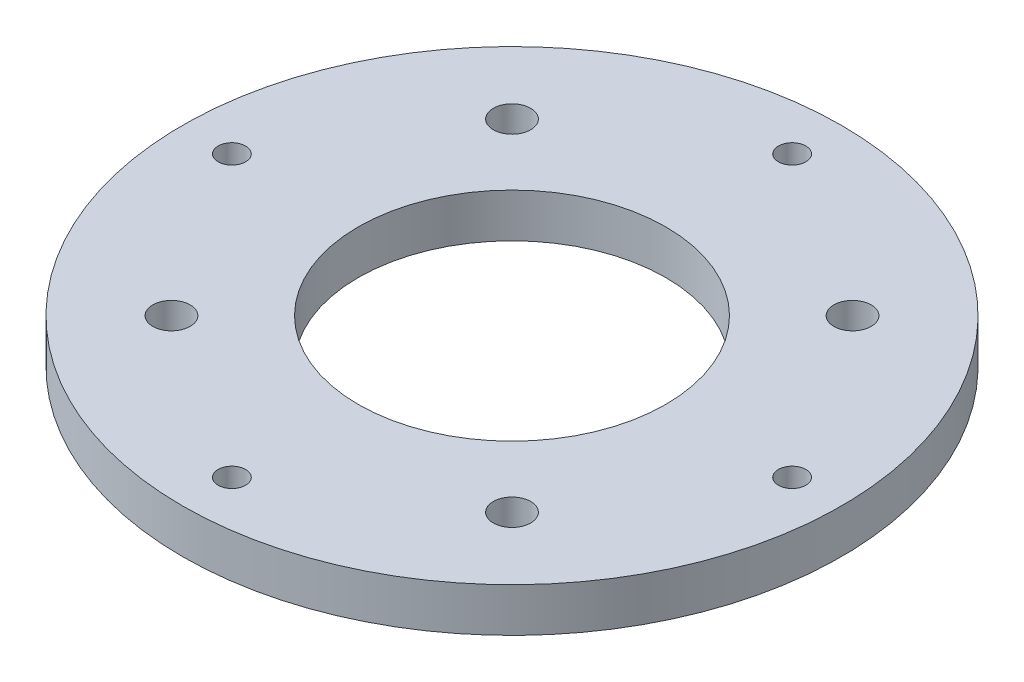
SolidWorks part; units mm, degrees
material "Acrylic (Medium-high impact)"
ref_plane "Front Plane" through (0, 0, 0) normal (0, 0, 1) x (1, 0, 0)
ref_plane "Top Plane" through (0, 0, 0) normal (0, 1, 0) x (1, 0, 0)
ref_plane "Right Plane" through (0, 0, 0) normal (1, 0, 0) x (0, 0, -1)
sketch "Sketch1" plane through (0, 0, 0) normal (0, 1, 0) x (1, 0, 0)
  circle A0 centre (0, 0) radius 30
  dimension "D1" = 60
base flange "Base-Flange1" sketch "Sketch1" thickness 4 reverse thickness direction no parameters "D1"=0.7366
sketch "Sketch6" plane through (0, 0, 0) normal (0, 1, 0) x (1, 0, 0)
  point P0 (0, 25.5)
  point P5 (25.5, 0)
  point P6 (0, -25.5)
  point P7 (-25.5, 0)
  dimension "D1" = 25.5
  dimension "D2" = 4
hole_wizard "M3 Tapped base" positions "Sketch6" profile "Sketch7" tap size "M3" standard "ISO" end condition through all
sketch "Sketch7" plane through (0, 0, -25.5) normal (1, 0, 0) x (0, 0, 1)
  line L0 (0, 0) -> (0, 4)
  line L1 (0, 4) -> (1.25, 4)
  line L2 (1.25, 4) -> (1.25, 0)
  line L5 (1.25, 0) -> (0, 0)
  line L11 (0, -6.35) -> (0, 107.95) construction
  dimension "Thru Tap Drill Dia." = 2.5
  dimension "Thru Tap Drill Depth" = 4
cosmetic thread "Hole Thread1"
cosmetic thread "Hole Thread2"
cosmetic thread "Hole Thread3"
cosmetic thread "Hole Thread4"
sketch "Sketch8" plane through (0, -4, 0) normal (0, -1, 0) x (1, 0, 0)
  line L1 (15.5, -15.5) -> (-15.5, -15.5) construction
  line L2 (15.5, -15.5) -> (15.5, 15.5) construction
  line L3 (15.5, 15.5) -> (-15.5, 15.5) construction
  line L4 (-15.5, -15.5) -> (-15.5, 15.5) construction
  line L5 (15.5, -15.5) -> (-15.5, 15.5) construction
  line L6 (15.5, 15.5) -> (-15.5, -15.5) construction
  circle A0 centre (0, 0) radius 21.9203 construction
  point P9 (15.5, 15.5)
  point P10 (-15.5, 15.5)
  point P11 (15.5, -15.5)
  point P12 (-15.5, -15.5)
  dimension "D1" = 31
hole_wizard "M3 Tapped motor" positions "Sketch8" profile "Sketch9" countersink size "M3" standard "ISO" end condition through all
sketch "Sketch9" plane through (-15.5, -4, -15.5) normal (1, 0, 0) x (0, 0, -1)
  line L0 (0, 0) -> (0, 4)
  line L1 (0, 4) -> (1.7, 4)
  line L2 (1.7, 4) -> (1.7, 1.45)
  line L3 (1.7, 1.45) -> (3.15, 0)
  line L5 (3.15, 0) -> (0, 0)
  line L6 (-1.7, 1.45) -> (-3.15, 0) construction
  line L11 (0, -6.35) -> (0, 107.95) construction
  dimension "Thru Hole Dia." = 3.4
  dimension "Thru Hole Depth" = 4
  dimension "Near C'Sink Dia." = 6.3
  dimension "Near C'Sink Angle" = 90
sketch "Sketch10" plane through (0, -4, 0) normal (0, -1, 0) x (-1, 0, 0)
  circle A0 centre (0, 0) radius 14
extrude "Cut-Extrude1" cut sketch "Sketch10" against normal through all normal cut yes
sketch "Bend-Lines1" [suppressed] plane through (0, 0, 0) normal (0, 1, 0) x (1, 0, 0)
sketch "Bounding-Box1" [suppressed] plane through (0, 0, 0) normal (0, 1, 0) x (1, 0, 0)
sheet metal parameters "Sheet-Metal1" thickness 4 parameters "D1"=0.7366
flat pattern "Flat-Pattern1" [suppressed]
sketch "Bend-Lines2" plane through (0, 0, 0) normal (0, 1, 0) x (1, 0, 0)
sketch3d "Bounding-Box2" [suppressed]
  line L0 (30.0261, 29.9738, 0) -> (29.9739, -30.0261, 0) construction
  line L1 (-29.9738, 30.0261, 0) -> (-30.0261, -29.9738, 0) construction
  line L2 (30.0261, 29.9738, 0) -> (-29.9738, 30.0261, 0) construction
  line L3 (29.9739, -30.0261, 0) -> (-30.0261, -29.9738, 0) construction
sheet metal parameters "Sheet-Metal2" thickness 4 parameters "D1"=0.7366
flat pattern "Flat-Pattern1"
sketch "Bend-Lines2" plane through (0, 0, 0) normal (0, 1, 0) x (1, 0, 0)
sketch3d "Bounding-Box2" [suppressed]
  line L0 (-30.0261, 29.9738, 0) -> (-29.9739, -30.0261, 0) construction
  line L1 (29.9738, 30.0261, 0) -> (30.0261, -29.9738, 0) construction
  line L2 (-30.0261, 29.9738, 0) -> (29.9738, 30.0261, 0) construction
  line L3 (-29.9739, -30.0261, 0) -> (30.0261, -29.9738, 0) construction
sheet metal parameters "Sheet-Metal3" thickness 4 parameters "D1"=0.7366
flat pattern "Flat-Pattern1"
sketch "Bend-Lines2" plane through (0, 0, 0) normal (0, 1, 0) x (1, 0, 0)
sketch3d "Bounding-Box2" [suppressed]
  line L0 (-30.0261, 29.9738, 0) -> (-29.9739, -30.0261, 0) construction
  line L1 (29.9738, 30.0261, 0) -> (30.0261, -29.9738, 0) construction
  line L2 (-30.0261, 29.9738, 0) -> (29.9738, 30.0261, 0) construction
  line L3 (-29.9739, -30.0261, 0) -> (30.0261, -29.9738, 0) construction
sheet metal parameters "Sheet-Metal4" thickness 4 parameters "D1"=0.7366
flat pattern "Flat-Pattern1"
sketch "Bend-Lines2"
sketch3d "Bounding-Box2" [suppressed]
  line L0 (-30.0261, 29.9738, 0) -> (-29.9739, -30.0261, 0) construction
  line L1 (29.9738, 30.0261, 0) -> (30.0261, -29.9738, 0) construction
  line L2 (-30.0261, 29.9738, 0) -> (29.9738, 30.0261, 0) construction
  line L3 (-29.9739, -30.0261, 0) -> (30.0261, -29.9738, 0) construction
